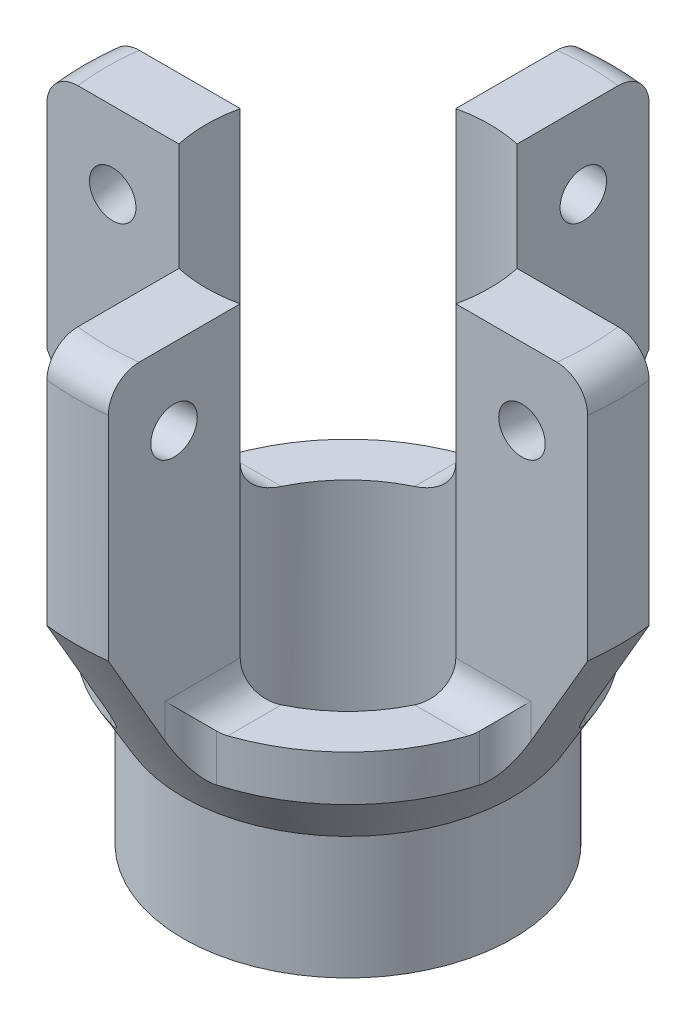
SolidWorks part; units mm, degrees
ref_plane "前视基准面" through (0, 0, 0) normal (0, 0, 1) x (1, 0, 0)
ref_plane "上视基准面" through (0, 0, 0) normal (0, 1, 0) x (1, 0, 0)
ref_plane "右视基准面" through (0, 0, 0) normal (1, 0, 0) x (0, 0, -1)
other "Configuration Table"
sketch "草图2" plane through (0, 0, 0) normal (0, 0, 1) x (1, 0, 0)
  line L0 (0, 66.749) -> (0, -26.3934) construction
  line L1 (21.5, 0) -> (18.5, 0)
  line L2 (21.5, 0) -> (21.5, 16)
  line L3 (18.5, 0) -> (18.5, 72)
  line L4 (21.5, 16) -> (35.5, 40.2487)
  line L5 (35.5, 40.2487) -> (35.5, 68)
  line L6 (31.5, 72) -> (18.5, 72)
  arc A0 (35.5, 68) -> (31.5, 72) centre (31.5, 68) ccw
  circle A1 centre (27, 62) radius 3
  point P15 (-2.0237, 48.0083)
  dimension "D1" = 4
  dimension "D5" = 6
  dimension "D2" = 37
  dimension "D3" = 72
  dimension "D4" = 3
  dimension "D6" = 10
  dimension "D7" = 54
  dimension "D8" = 17
  dimension "D9" = 150
  dimension "D10" = 16
revolve "旋转2" add sketch "草图2" angle 360 about L0
sketch "草图3" plane through (0, 72, 0) normal (0, 1, 0) x (1, 0, 0)
  line L0 (0, -25) -> (0, -51.6999) construction
  line L1 (4, -35.2739) -> (4, -18.0624)
  line L2 (-4, -35.2739) -> (-4, -18.0624)
  line L3 (-35.2739, 4) -> (-18.0624, 4)
  line L4 (-35.2739, -4) -> (-18.0624, -4)
  line L5 (-25, 0) -> (-51.6999, 0) construction
  line L6 (4, 35.2739) -> (4, 18.0624)
  line L7 (-4, 35.2739) -> (-4, 18.0624)
  line L8 (0, 25) -> (0, 51.6999) construction
  line L9 (35.2739, -4) -> (18.0624, -4)
  line L10 (35.2739, 4) -> (18.0624, 4)
  line L11 (25, 0) -> (51.6999, 0) construction
  circle A0 centre (0, 0) radius 35.5 construction
  arc A1 (-4, 35.2739) -> (-35.2739, 4) centre (0, 0) ccw
  circle A2 centre (0, 0) radius 18.5 construction
  arc A5 (35.2739, 4) -> (4, 35.2739) centre (0, 0) ccw
  arc A7 (4, -35.2739) -> (35.2739, -4) centre (0, 0) ccw
  arc A8 (-35.2739, -4) -> (-4, -35.2739) centre (0, 0) ccw
  circle A10 centre (0, 0) radius 25
  circle A11 centre (0, 0) radius 18.5
  point P20 (-4, -18.0624)
  point P31 (0, 0)
  circle M7 centre (0, 0) radius 18.5
  circle M8 centre (0, 0) radius 31.5
  dimension "D3" = 50
  dimension "D1" = 8
  dimension "D2" = 4
extrude "切除-拉伸6" cut sketch "草图3" against normal blind 100 contours L4 A8 L2 M8 | L1 A7 L9 M8 | L10 A5 L6 M8 | L7 A1 L3 M8 | A10 L4 L2 M8 | A10 L7 L3 M8 | A10 L10 L6 M8 | A10 L1 L9 M8 region at (4.4423, 72, 33.2595) region at (18.7231, 72, 18.7231) region at (-18.7231, 72, 18.7231) region at (-4.4423, 72, 33.2595) region at (-18.7231, 72, -18.7231) region at (-33.2595, 72, -4.4423) region at (22.5866, 72, -22.5866) region at (18.7231, 72, -18.7231)
extrude "切除-拉伸8" cut sketch "草图3<6>" against normal blind 44 contours L4 A10 L2 M7 | L1 A10 L9 M7 | L10 A10 L6 M7 | L7 A10 L3 M7 region at (14.6073, 72, 14.6073) region at (-14.6073, 72, 14.6073) region at (-14.6073, 72, -14.6073) region at (14.6073, 72, -14.6073)
sketch "草图3<6>" plane through (0, 72, 0) normal (0, 1, 0) x (1, 0, 0) same geometry as "草图3"
fillet "圆角2" radius 4 16 edges at (4, 25.0311, 24.6779) (4, 28, 21.3702) (24.6779, 25.0311, 4) (21.3702, 28, 4) (-24.6779, 25.0311, 4) (-21.3702, 28, 4) (-4, 25.0311, 24.6779) (-4, 28, 21.3702) (-24.6779, 25.0311, -4) (-21.3702, 28, -4) (-4, 25.0311, -24.6779) (-4, 28, -21.3702) (4, 25.0311, -24.6779) (4, 28, -21.3702) (21.3702, 28, -4) (24.6779, 25.0311, -4)
